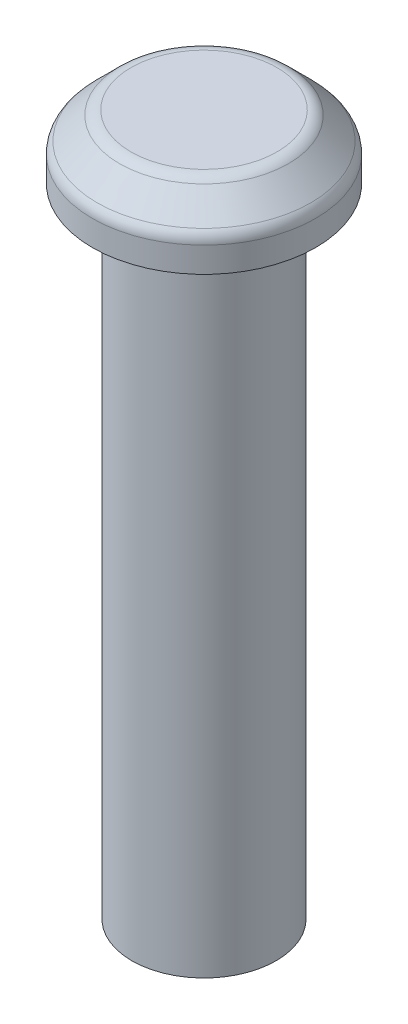
SolidWorks part; units mm, degrees
ref_plane "Front Plane" through (0, 0, 0) normal (0, 0, 1) x (1, 0, 0)
ref_plane "Top Plane" through (0, 0, 0) normal (0, 1, 0) x (1, 0, 0)
ref_plane "Right Plane" through (0, 0, 0) normal (1, 0, 0) x (0, 0, -1)
sketch "Sketch1" plane through (0, 0, 0) normal (0, 1, 0) x (1, 0, 0)
  circle A0 centre (0, 0) radius 2.265
  dimension "D1" = 4.53
extrude "Boss-Extrude1" add sketch "Sketch1" along normal blind 20
sketch "Sketch2" plane through (0, 20, 0) normal (0, 1, 0) x (1, 0, 0)
  circle A0 centre (0, 0) radius 3.5
  dimension "D1" = 7
extrude "Boss-Extrude2" add sketch "Sketch2" along normal blind 2
chamfer "Chamfer1" distance 1 angle 45 1 edges at (0, 22, 3.5)
fillet "Fillet1" radius 0.5 2 edges at (0, 21, 3.5) (0, 22, 2.5)
